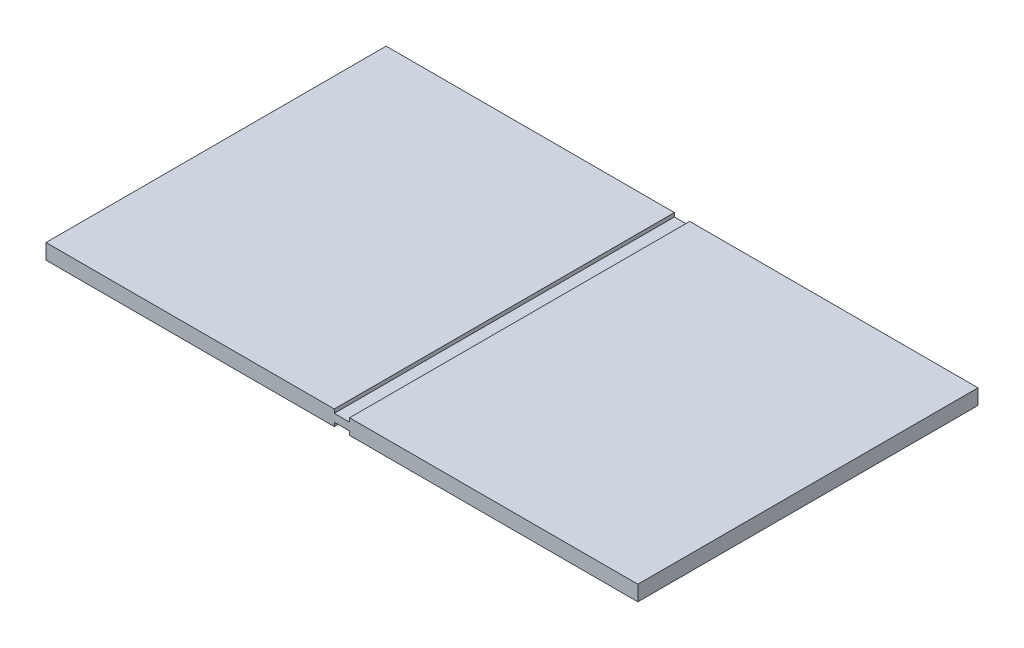
SolidWorks part; units mm, degrees
ref_plane "Front" through (0, 0, 0) normal (0, 0, 1) x (1, 0, 0)
ref_plane "Top" through (0, 0, 0) normal (0, 1, 0) x (1, 0, 0)
ref_plane "Right" through (0, 0, 0) normal (1, 0, 0) x (0, 0, -1)
sketch "Sketch1" plane through (0, 0, 0) normal (0, 1, 0) x (1, 0, 0)
  line L1 (-348, -200) -> (348, -200)
  line L2 (-348, -200) -> (-348, 200)
  line L3 (-348, 200) -> (348, 200)
  line L4 (348, -200) -> (348, 200)
  line L5 (-348, -200) -> (348, 200) construction
  line L6 (-348, 200) -> (348, -200) construction
  point P0 (0, 0)
  dimension "D1" = 696
  dimension "D2" = 400
extrude "Boss-Extrude1" add sketch "Sketch1" along normal blind 18
sketch "Sketch2" plane through (0, 18, 0) normal (0, 1, 0) x (1, 0, 0)
  line L0 (348, 200) -> (-348, 200) construction
  line L1 (9, -200) -> (-9, -200)
  line L2 (9, -200) -> (9, 200)
  line L3 (9, 200) -> (-9, 200)
  line L4 (-9, -200) -> (-9, 200)
  line L5 (9, -200) -> (-9, 200) construction
  line L6 (9, 200) -> (-9, -200) construction
  point P0 (0, 0)
  dimension "D1" = 18
extrude "Cut-Extrude1" cut sketch "Sketch2" against normal blind 4.5
sketch "Sketch3" plane through (0, 0, 0) normal (0, -1, 0) x (-1, 0, 0)
  line L0 (348, -200) -> (-348, -200) construction
  line L1 (9, 200) -> (-9, 200)
  line L2 (9, 200) -> (9, -200)
  line L3 (9, -200) -> (-9, -200)
  line L4 (-9, 200) -> (-9, -200)
  line L5 (9, 200) -> (-9, -200) construction
  line L6 (9, -200) -> (-9, 200) construction
  point P0 (0, 0)
  dimension "D1" = 18
extrude "Cut-Extrude2" cut sketch "Sketch3" against normal blind 4.5
